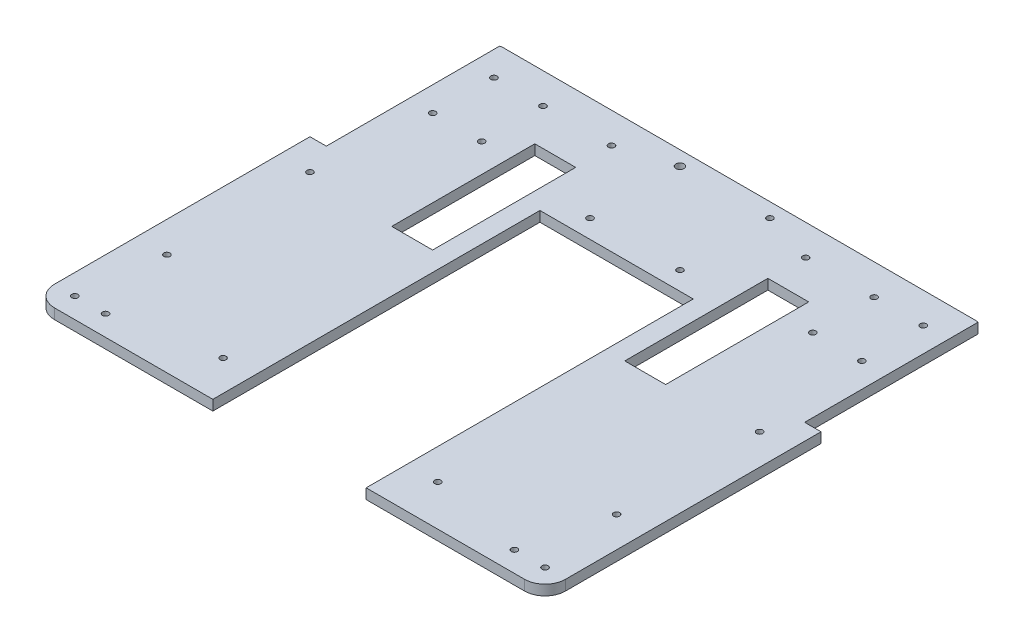
SolidWorks part; units mm, degrees
ref_plane "前视基准面" through (0, 0, 0) normal (0, 0, 1) x (1, 0, 0)
ref_plane "上视基准面" through (0, 0, 0) normal (0, 1, 0) x (1, 0, 0)
ref_plane "右视基准面" through (0, 0, 0) normal (1, 0, 0) x (0, 0, -1)
sketch "草图1" plane through (0, 0, 0) normal (0, 1, 0) x (1, 0, 0)
  line L1 (10, 0) -> (240, 0)
  line L2 (0, -10) -> (0, -210)
  line L3 (10, -220) -> (240, -220)
  line L4 (250, -10) -> (250, -210)
  arc A0 (0, -210) -> (10, -220) centre (10, -210) ccw
  arc A1 (240, -220) -> (250, -210) centre (240, -210) ccw
  arc A2 (240, 0) -> (250, -10) centre (240, -10) cw
  arc A3 (10, 0) -> (0, -10) centre (10, -10) ccw
  point P9 (250, -220)
  point P12 (250, 0)
  point P15 (0, 0)
  dimension "D3" = 10
  dimension "D1" = 250
  dimension "D2" = 220
extrude "凸台-拉伸1" add sketch "草图1" along normal blind 5
sketch "草图5" plane through (0, 0, 0) normal (0, -1, 0) x (1, 0, 0)
  line L0 (125, 220) -> (125, 0) construction
  line L1 (10, 220) -> (240, 220) construction
  line L2 (240, 0) -> (10, 0) construction
  line L3 (87.5, 220) -> (162.5, 220) construction
  line L4 (87.5, 220) -> (87.5, 60)
  line L5 (162.5, 220) -> (87.5, 220)
  line L6 (162.5, 220) -> (162.5, 60)
  line L7 (162.5, 60) -> (87.5, 60)
  point P11 (125, 60)
  dimension "D1" = 37.5
  dimension "D2" = 160
extrude "切除-拉伸4" cut sketch "草图5" against normal blind 5
sketch "草图6" plane through (0, 0, 0) normal (0, -1, 0) x (1, 0, 0)
  line L0 (72.5, 220) -> (72.5, 200) construction
  line L1 (10, 220) -> (87.5, 220) construction
  line L2 (72.5, 200) -> (87.5, 200) construction
  line L7 (87.5, 220) -> (87.5, 60) construction
  line L8 (125, 60) -> (125, 181.8158) construction
  line L9 (87.5, 60) -> (162.5, 60) construction
  line L10 (87.5, 60) -> (87.5, 0) construction
  line L11 (240, 0) -> (10, 0) construction
  line L12 (87.5, 20) -> (92.5, 20) construction
  line L13 (92.5, 20) -> (92.5, 0) construction
  line L14 (92.5, 20) -> (107.5, 20) construction
  circle A0 centre (72.5, 200) radius 1.5
  circle A3 centre (177.5, 200) radius 1.5
  dimension "D3" = 3
  dimension "D1" = 20
  dimension "D2" = 15
  dimension "D4" = 5
  dimension "D5" = 20
  dimension "D6" = 15
extrude "切除-拉伸5" cut sketch "草图6" against normal up to next contours A0 | A3
sketch "草图8" plane through (0, 0, 0) normal (0, -1, 0) x (1, 0, 0)
  line L0 (250, 170) -> (235, 170) construction
  line L1 (250, 210) -> (250, 10) construction
  line L2 (235, 170) -> (235, 220) construction
  line L3 (162.5, 220) -> (240, 220) construction
  line L4 (235, 170) -> (235, 100) construction
  line L5 (235, 100) -> (250, 100) construction
  line L6 (125, 60) -> (125, 122.441) construction
  line L7 (87.5, 60) -> (162.5, 60) construction
  line L8 (15, 170) -> (15, 100) construction
  circle A0 centre (235, 170) radius 1.5
  circle A1 centre (235, 100) radius 1.5
  circle A2 centre (15, 100) radius 1.5
  circle A3 centre (15, 170) radius 1.5
  dimension "D4" = 3
  dimension "D5" = 3
  dimension "D1" = 15
  dimension "D2" = 50
  dimension "D3" = 70
extrude "切除-拉伸8" cut sketch "草图8" against normal up to next
sketch "草图9" plane through (0, 0, 0) normal (0, -1, 0) x (1, 0, 0)
  line L0 (87.5, 60) -> (87.5, 0) construction
  line L1 (240, 0) -> (10, 0) construction
  line L2 (87.5, 0) -> (87.5, 15) construction
  line L3 (87.5, 15) -> (77.5, 15) construction
  line L4 (10, 220) -> (10, 210) construction
  line L5 (125, 60) -> (125, 0) construction
  line L6 (87.5, 60) -> (162.5, 60) construction
  circle A0 centre (77.5, 15) radius 1.5
  circle A1 centre (10, 210) radius 1.5
  circle A2 centre (240, 210) radius 1.5
  circle A3 centre (172.5, 15) radius 1.5
  dimension "D3" = 3
  dimension "D4" = 3
  dimension "D1" = 15
  dimension "D2" = 10
extrude "切除-拉伸9" cut sketch "草图9" against normal up to next
sketch "草图10" plane through (0, 0, 0) normal (0, -1, 0) x (1, 0, 0)
  line L0 (125, 60) -> (125, 0) construction
  line L1 (0, 0) -> (8, 0)
  line L2 (0, 0) -> (0, 85)
  line L3 (0, 85) -> (8, 85)
  line L4 (8, 0) -> (8, 85)
  line L5 (87.5, 60) -> (162.5, 60) construction
  line L6 (240, 0) -> (10, 0) construction
  line L7 (242, 0) -> (242, 85)
  line L8 (250, 85) -> (242, 85)
  line L9 (250, 0) -> (250, 85)
  line L10 (250, 0) -> (242, 0)
  dimension "D1" = 8
  dimension "D2" = 85
extrude "切除-拉伸10" cut sketch "草图10" against normal up to next
sketch "草图11" plane through (0, 0, 0) normal (0, -1, 0) x (1, 0, 0)
  line L0 (10, 210) -> (25, 210) construction
  line L1 (125, 60) -> (125, 137.5337) construction
  line L2 (87.5, 60) -> (162.5, 60) construction
  circle A0 centre (25, 210) radius 1.5
  circle A1 centre (225, 210) radius 1.5
  dimension "D2" = 3
  dimension "D1" = 15
extrude "切除-拉伸11" cut sketch "草图11" against normal blind 10
sketch "草图12" plane through (0, 0, 0) normal (0, -1, 0) x (1, 0, 0)
  line L0 (125, 0) -> (125, 25.6074) construction
  line L1 (240, 0) -> (10, 0) construction
  circle A0 centre (230, 15) radius 1.5 construction
  circle A1 centre (230, 15) radius 1.5
  circle A2 centre (206, 15) radius 1.5 construction
  circle A3 centre (206, 15) radius 1.5
  circle A4 centre (230, 45) radius 1.5 construction
  circle A5 centre (230, 45) radius 1.5
  circle A6 centre (206, 45) radius 1.5 construction
  circle A7 centre (206, 45) radius 1.5
  circle A8 centre (44, 45) radius 1.5
  circle A9 centre (20, 45) radius 1.5
  circle A10 centre (44, 15) radius 1.5
  circle A11 centre (20, 15) radius 1.5
extrude "切除-拉伸12" cut sketch "草图12" against normal blind 10
sketch "草图13" plane through (0, 0, 0) normal (0, -1, 0) x (1, 0, 0)
  line L0 (240, 0) -> (10, 0) construction
  line L1 (78, 33) -> (58, 33)
  line L2 (78, 33) -> (78, 103)
  line L3 (78, 103) -> (58, 103)
  line L4 (58, 33) -> (58, 103)
  line L5 (8, 0.202) -> (8, 85) construction
  line L6 (125, 60) -> (125, 0) construction
  line L7 (87.5, 60) -> (162.5, 60) construction
  line L8 (192, 33) -> (192, 103)
  line L9 (172, 103) -> (192, 103)
  line L10 (172, 33) -> (172, 103)
  line L11 (172, 33) -> (192, 33)
  dimension "D1" = 70
  dimension "D2" = 20
  dimension "D3" = 33
  dimension "D4" = 50
extrude "切除-拉伸13" cut sketch "草图13" against normal blind 10
sketch "草图14" plane through (0, 0, 0) normal (0, -1, 0) x (1, 0, 0)
  line L0 (125, 60) -> (125, 0) construction
  line L1 (87.5, 60) -> (162.5, 60) construction
  line L3 (240, 0) -> (10, 0) construction
  line L4 (103, 51) -> (147, 51) construction
  line L5 (103, 51) -> (103, 7) construction
  line L6 (103, 7) -> (147, 7) construction
  line L7 (147, 51) -> (147, 7) construction
  line L8 (103, 51) -> (147, 7) construction
  line L9 (103, 7) -> (147, 51) construction
  circle A0 centre (103, 7) radius 2
  circle A1 centre (103, 51) radius 1.5
  circle A2 centre (147, 51) radius 1.5
  circle A3 centre (147, 7) radius 1.5
  point P6 (125, 29)
  dimension "D4" = 4
  dimension "D5" = 3
  dimension "D6" = 3
  dimension "D7" = 3
  dimension "D1" = 44
  dimension "D2" = 44
  dimension "D3" = 7
extrude "切除-拉伸14" cut sketch "草图14" against normal blind 10
